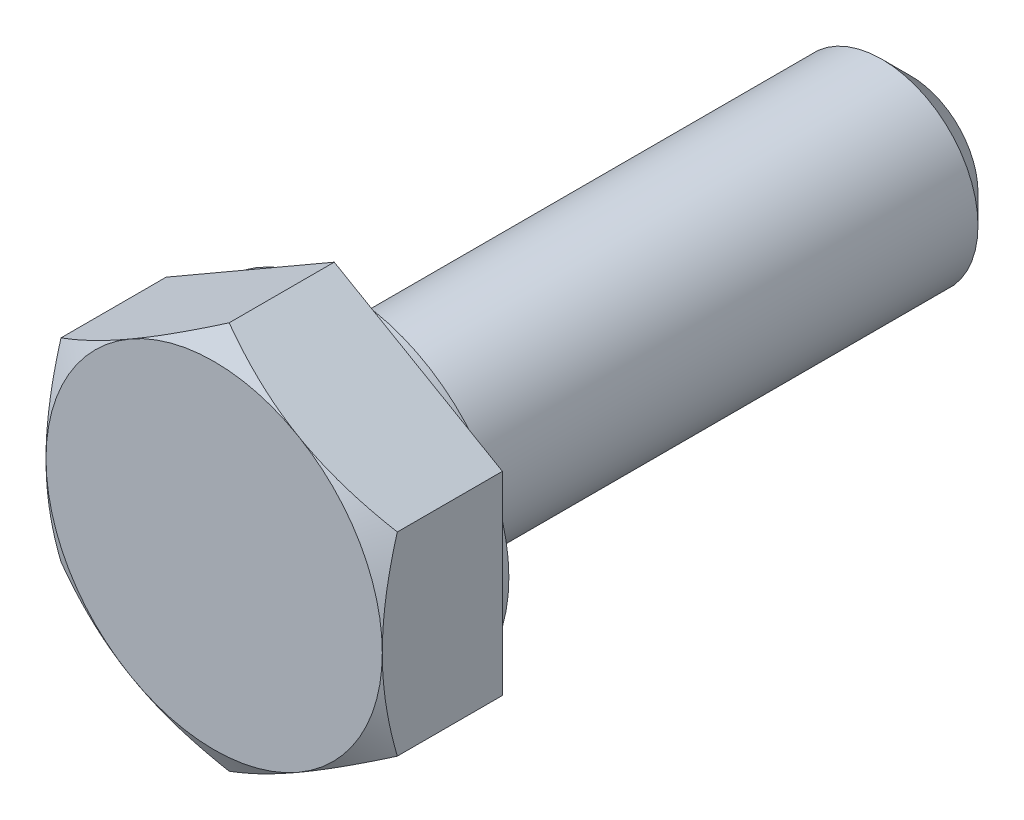
SolidWorks part; units mm, degrees
ref_plane "Front Plane" through (0, 0, 0) normal (0, 0, 1) x (1, 0, 0)
ref_plane "Top Plane" through (0, 0, 0) normal (0, 1, 0) x (1, 0, 0)
ref_plane "Right Plane" through (0, 0, 0) normal (1, 0, 0) x (0, 0, -1)
sketch "Sketch1" plane through (0, 0, 0) normal (1, 0, 0) x (0, 0, -1)
  line L0 (0, 0) -> (19.05, 0) construction
  line L1 (19.05, 3.175) -> (19.05, -3.175) construction
  line L2 (0, 5.5563) -> (0, -5.5563) construction
  line L3 (0, 0) -> (-3.9687, 0) construction
  line L4 (-3.9688, 5.5563) -> (-3.9687, -5.5562) construction
  line L5 (18.9706, 3.3125) -> (20.2406, 3.3125) construction
  line L6 (20.2406, 3.3125) -> (19.6056, 2.2126) construction
  line L7 (19.6056, 2.2126) -> (18.9706, 3.3125) construction
  line L8 (19.0103, 3.2437) -> (20.2009, 3.2437) construction
  line L9 (19.05, 3.175) -> (20.1613, 3.175) construction
  line L10 (19.5262, 2.3501) -> (19.685, 2.3501) construction
  line L11 (19.6056, 3.3125) -> (19.6056, 3.175) construction
  line L12 (19.6056, 2.3501) -> (19.6056, 2.2126) construction
  point P5 (19.05, 0)
  point P9 (0, 0)
  point P13 (-3.9687, 0)
  point P18 (15.875, -3.175)
  point P25 (19.6056, 3.2437)
  dimension "Length" = 19.05
  dimension "Thread OD" = 6.35
  dimension "Hex Width" = 11.1125
  dimension "Hex Height" = 3.9688
  dimension "D1" = 60
  dimension "Pitch" = 1.27
  dimension "D2" = 0.1588
  dimension "D3" = 3.175
sketch "Sketch2" plane through (0, 0, 0) normal (1, 0, 0) x (0, 0, -1)
  line L0 (0, 0) -> (19.05, 0)
  line L1 (0, 5.5563) -> (0, -5.5563) construction
  line L2 (19.05, 0) -> (19.05, 3.175)
  line L3 (19.05, 3.175) -> (0, 3.175)
  line L4 (0, 3.175) -> (0, 0)
revolve "Revolve1" add sketch "Sketch2" angle 360 about L0
sketch "Sketch3" plane through (0, 0, 0) normal (0, 0, 1) x (1, 0, 0)
  line L1 (0, 6.4158) -> (-5.5562, 3.2079)
  line L2 (-5.5562, 3.2079) -> (-5.5562, -3.2079)
  line L3 (-5.5562, -3.2079) -> (0, -6.4158)
  line L4 (0, -6.4158) -> (5.5562, -3.2079)
  line L5 (5.5562, -3.2079) -> (5.5562, 3.2079)
  line L6 (5.5562, 3.2079) -> (0, 6.4158)
  circle A0 centre (0, 0) radius 5.5563 construction
extrude "Boss-Extrude1" add sketch "Sketch3" along normal up to vertex (3.9688 mm away) up to point (0, 0, 3.9687)
sketch "Sketch7" plane through (0, 0, 0) normal (0, 0, -1) x (-1, 0, 0)
  circle A4 centre (0, 0) radius 5.4928
  circle A5 centre (0, 0) radius 5.4928
  dimension "D1" = 0.0635
extrude "Boss-Extrude2" add sketch "Sketch7" along normal blind 0.2778
chamfer "Chamfer1" distance 0.9525 angle 45 1 edges at (3.175, 0, -19.05)
sketch "Sketch4" plane through (0, 0, 3.9687) normal (0, 0, 1) x (1, 0, 0)
  circle A0 centre (0, 0) radius 5.5563
extrude "Cut-Extrude1" cut sketch "Sketch4" against normal through all draft 60 flip side to cut
ref_axis "Center Axis 1" through (0, 0, -40.7048) along (0, 0, 1)
split "Split1" [suppressed] bodies to split 106
sketch "Sketch5" [suppressed] plane through (0, 0, 0) normal (1, 0, 0) x (0, 0, -1)
  line L0 (19.0103, 3.2437) -> (20.2009, 3.2437)
  line L1 (19.0103, 3.2437) -> (19.5262, 2.3501)
  line L2 (19.5262, 2.3501) -> (19.685, 2.3501)
  line L3 (20.2009, 3.2437) -> (19.685, 2.3501)
sketch "Sketch6" [suppressed] plane through (0, 0, -19.05) normal (0, 0, -1) x (-1, 0, 0)
  circle A0 centre (0, 0) radius 3.175
curve "Helix/Spiral1" [suppressed] pitch 1.27 height 20.32 turns 16
sweep "Cut-Sweep1" [suppressed] cut profiles "Sketch5" path "Helix/Spiral1"
combine bodies "Combine1" [suppressed] operation type add bodies to combine 108 109
sketch "Sketch8" [suppressed] plane through (0, 0, -0.2778) normal (0, 0, -1) x (-1, 0, 0)
  circle A0 centre (0, 0) radius 5.4928 construction
  circle A1 centre (0, 0) radius 5.4928
extrude "Boss-Extrude3" [suppressed] add sketch "Sketch8" against normal up to surface (0.2778 mm away)
equation "\"D2@Sketch1\"=\"Pitch@Sketch1\"/8"
equation "\"D1@Chamfer1\"=\"Pitch@Sketch1\"*.75"
equation "\"D4@Helix/Spiral1\"=\"Pitch@Sketch1\""
equation "\"D3@Helix/Spiral1\"=\"Length@Sketch1\"+\"Pitch@Sketch1\""
equation "\"D3@Sketch1\"=\"Pitch@Sketch1\"*2.5"
equation "\"D1@Boss-Extrude2\"=\"Hex Width@Sketch1\"*.025"
